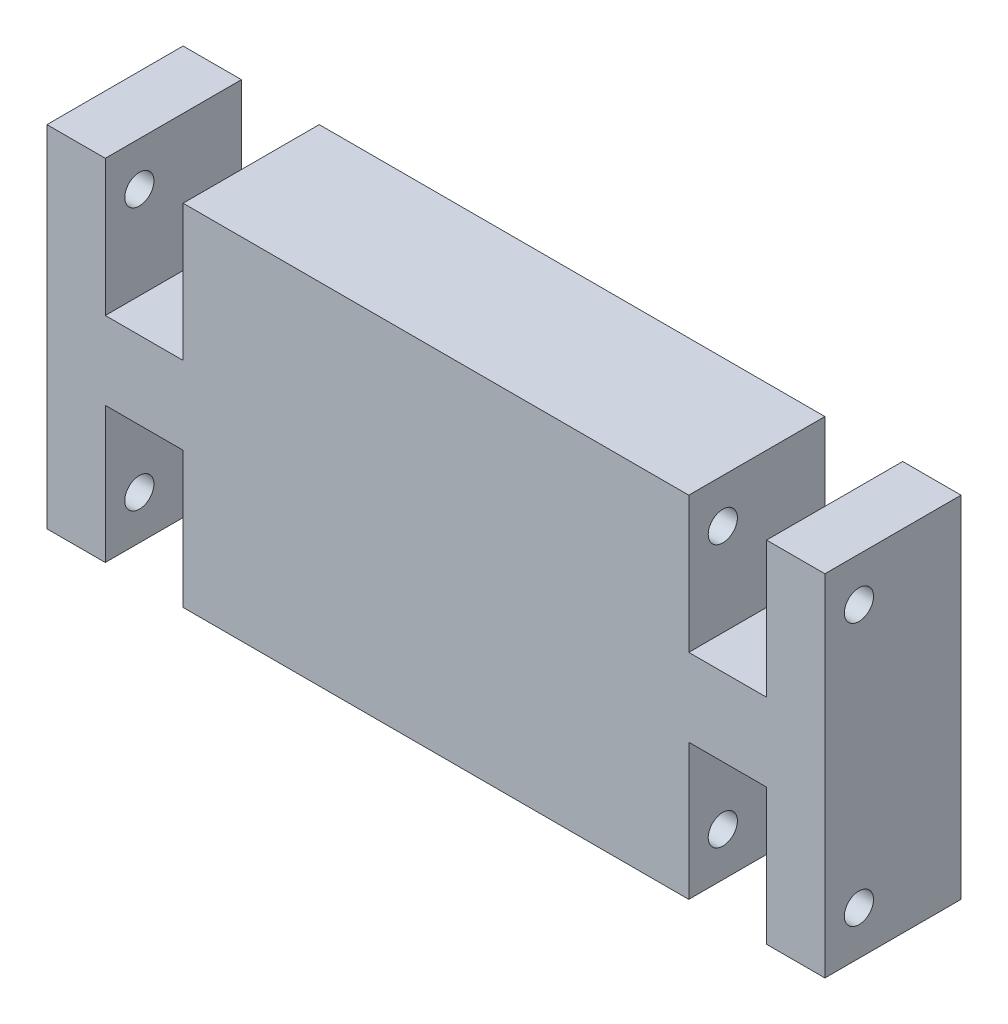
SolidWorks part; units mm, degrees
ref_plane "Alzado" through (0, 0, 0) normal (0, 0, 1) x (1, 0, 0)
ref_plane "Planta" through (0, 0, 0) normal (0, 1, 0) x (1, 0, 0)
ref_plane "Vista lateral" through (0, 0, 0) normal (1, 0, 0) x (0, 0, -1)
sketch "Croquis2" plane through (0, 0, 0) normal (0, 0, 1) x (1, 0, 0)
  line L1 (0, 0) -> (400, 0)
  line L2 (0, 0) -> (0, 180)
  line L3 (0, 180) -> (400, 180)
  line L4 (400, 0) -> (400, 180)
  dimension "D1" = 400
  dimension "D2" = 180
extrude "Saliente-Extruir3" add sketch "Croquis2" along normal blind 70
sketch "Croquis3" plane through (0, 0, 70) normal (0, 0, 1) x (1, 0, 0)
  line L0 (0, 90) -> (400, 90)
  line L1 (0, 180) -> (0, 0) construction
  line L2 (400, 0) -> (400, 180) construction
  line L3 (0, 0) -> (400, 0) construction
  line L4 (30, 0) -> (70, 0)
  line L5 (30, 0) -> (30, 70)
  line L6 (30, 70) -> (70, 70)
  line L7 (70, 0) -> (70, 70)
  line L8 (30, 0) -> (0, 0)
  line L9 (200, 90) -> (200, 0)
  line L10 (370, 0) -> (400, 0)
  line L11 (330, 0) -> (330, 70)
  line L12 (370, 70) -> (330, 70)
  line L13 (370, 0) -> (370, 70)
  line L14 (370, 0) -> (330, 0)
  line L15 (370, 180) -> (330, 180)
  line L16 (370, 180) -> (370, 110)
  line L17 (370, 110) -> (330, 110)
  line L18 (330, 180) -> (330, 110)
  line L19 (370, 180) -> (400, 180)
  line L20 (30, 180) -> (0, 180)
  line L21 (70, 180) -> (70, 110)
  line L22 (30, 110) -> (70, 110)
  line L23 (30, 180) -> (30, 110)
  line L24 (30, 180) -> (70, 180)
  line M9 (0, 0) -> (400, 0)
  line M11 (400, 180) -> (0, 180)
  dimension "D1" = 40
  dimension "D2" = 70
  dimension "D3" = 30
extrude "Cortar-Extruir1" cut sketch "Croquis3" against normal blind 70 contours L23 L22 L21 M11 | L13 L12 L11 M9 | L7 L6 L5 M9 | L16 L17 L18 L15 region at (50, 35, 70) region at (350, 35, 70) region at (50, 145, 70)
sketch "Croquis4" plane through (400, 0, 0) normal (1, 0, 0) x (0, 0, -1)
  line L0 (-70, 180) -> (-35, 135) construction
  line L1 (-70, 180) -> (-35, 180) construction
  line L2 (-70, 180) -> (-70, 135) construction
  line L3 (-70, 135) -> (-35, 135) construction
  line L4 (-35, 180) -> (-35, 135) construction
  line L5 (0, 90) -> (-70, 90) construction
  line L6 (0, 0) -> (0, 180) construction
  line L7 (-70, 0) -> (-70, 180) construction
  circle A0 centre (-52.5, 157.5) radius 7.5
  circle A1 centre (-52.5, 22.5) radius 7.5
  dimension "D3" = 15
  dimension "D1" = 45
  dimension "D2" = 35
extrude "Cortar-Extruir2" cut sketch "Croquis4" against normal blind 400
